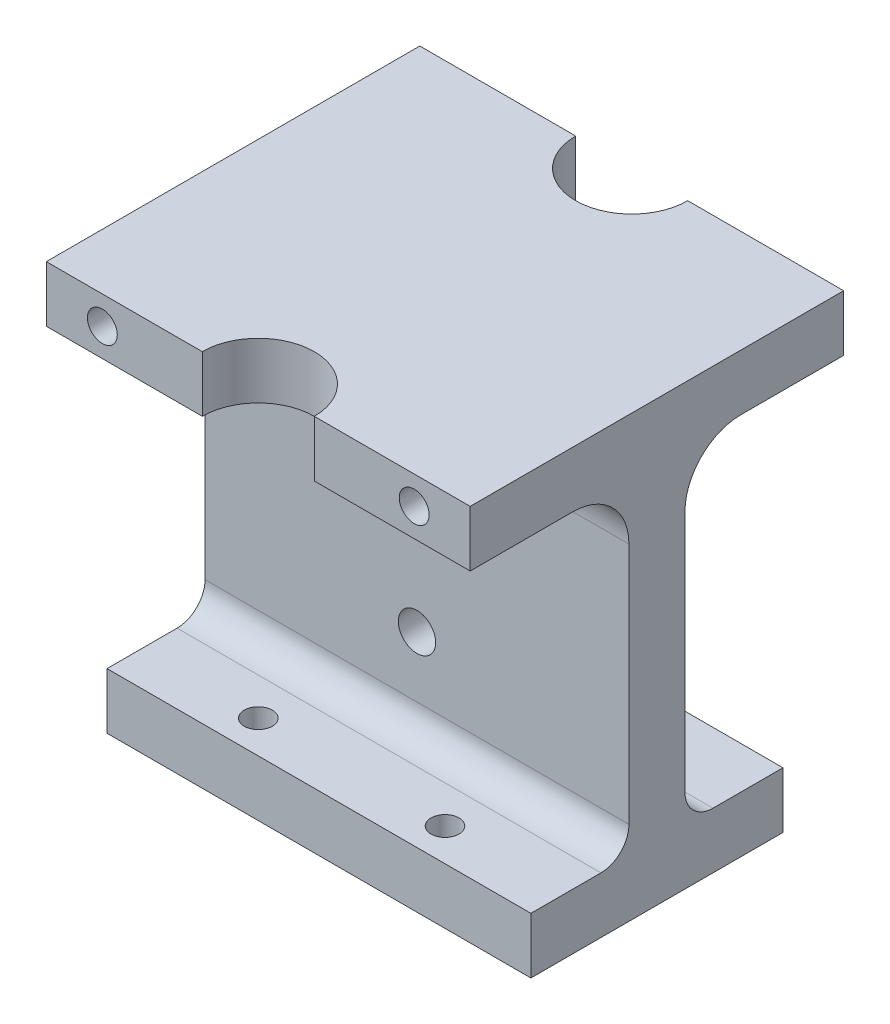
SolidWorks part; units mm, degrees
ref_plane "Płaszczyzna przednia" through (0, 0, 0) normal (0, 0, 1) x (1, 0, 0)
ref_plane "Płaszczyzna górna" through (0, 0, 0) normal (0, 1, 0) x (1, 0, 0)
ref_plane "Płaszczyzna prawa" through (0, 0, 0) normal (1, 0, 0) x (0, 0, -1)
sketch "Sketch1" plane through (0, 0, 0) normal (0, 1, 0) x (1, 0, 0)
  line L1 (0, 0) -> (45.4, 0)
  line L2 (0, 0) -> (0, 27)
  line L3 (0, 27) -> (45.4, 27)
  line L4 (45.4, 0) -> (45.4, 27)
  dimension "D1" = 45.4
  dimension "D2" = 27
extrude "Boss-Extrude1" add sketch "Sketch1" along normal blind 6
sketch "Sketch4" plane through (0, 6, 0) normal (0, 1, 0) x (1, 0, 0)
  line L0 (0, 27) -> (0, 0) construction
  line L1 (0, 16.5) -> (45.4, 16.5)
  line L2 (0, 16.5) -> (0, 10.5)
  line L3 (0, 10.5) -> (45.4, 10.5)
  line L4 (45.4, 16.5) -> (45.4, 10.5)
  line L5 (45.4, 0) -> (45.4, 27) construction
  line L6 (0, 0) -> (45.4, 0) construction
  dimension "D1" = 6
  dimension "D2" = 10.5
extrude "Boss-Extrude2" add sketch "Sketch4" along normal blind 35
sketch "Sketch5" plane through (0, 41, 0) normal (0, 1, 0) x (1, 0, 0)
  line L0 (45.4, 13.5) -> (0, 13.5) construction
  line L1 (45.4, 33.5) -> (28.7, 33.5)
  line L2 (45.4, 33.5) -> (45.4, -6.5)
  line L3 (45.4, -6.5) -> (28.7, -6.5)
  line L4 (0, 33.5) -> (0, -6.5)
  line L5 (45.4, 33.5) -> (0, -6.5) construction
  line L6 (45.4, -6.5) -> (0, 33.5) construction
  line L7 (45.4, 10.5) -> (45.4, 16.5) construction
  line L8 (0, 16.5) -> (0, 10.5) construction
  line L9 (16.7, 33.5) -> (0, 33.5)
  line L10 (16.7, -6.5) -> (0, -6.5)
  line L11 (22.7, 33.5) -> (22.7, -6.5) construction
  line L12 (45.4, 33.5) -> (0, 33.5) construction
  line L13 (15.0168, -6.5) -> (31.9525, -6.5) construction
  arc A0 (16.7, 33.5) -> (28.7, 33.5) centre (22.7, 33.5) ccw
  arc A1 (28.7, -6.5) -> (16.7, -6.5) centre (22.7, -6.5) ccw
  point P4 (22.7, 13.5)
  dimension "D2" = 6
  dimension "D3" = 6
  dimension "D4" = 22.7
  dimension "D1" = 40
extrude "Boss-Extrude3" add sketch "Sketch5" along normal blind 6
fillet "Fillet4" radius 6 2 edges at (22.7, 41, -10.5) (22.7, 41, -16.5)
hole_wizard "Ø3.2 (3.2) Diameter Hole1" positions "Sketch6" profile "Sketch7" hole size "Ø3.2" standard "ANSI Metric" end condition through all
sketch "Sketch6" plane through (0, 0, 6.5) normal (0, 0, 1) x (1, 0, 0)
  line L0 (0, 47) -> (0, 41) construction
  line L1 (0, 41) -> (16.7, 41) construction
  line L2 (45.4, 47) -> (45.4, 41) construction
  point P0 (6, 44)
  point P2 (39.4, 44)
  dimension "D1" = 6
  dimension "D2" = 3
  dimension "D3" = 6
sketch "Sketch7" plane through (6, 44, 6.5) normal (1, 0, 0) x (0, -1, 0)
  line L0 (0, 0) -> (0, 40)
  line L1 (0, 40) -> (1.6, 40)
  line L2 (1.6, 40) -> (1.6, 0)
  line L5 (1.6, 0) -> (0, 0)
  line L11 (0, -6.35) -> (0, 107.95) construction
  dimension "Thru Hole Dia." = 3.2
  dimension "Thru Hole Depth" = 40
ref_plane "Plane4" through (22.7, 0, 0) normal (-1, 0, 0) x (0, 0, 1)
hole_wizard "Ø3.0mm Dowel Hole1" positions "Sketch13" profile "Sketch14" hole size "Ø3.0" standard "ANSI Metric" end condition through all
sketch "Sketch13" plane through (0, 6, 0) normal (0, 1, 0) x (1, 0, 0)
  line L0 (45.4, 27) -> (0, 27) construction
  line L1 (0, 27) -> (0, 16.5) construction
  point P0 (12.7, 23.5)
  point P10 (32.7, 23.5)
  point P11 (32.7, 3.5)
  point P12 (12.7, 3.5)
  dimension "D1" = 3.5
  dimension "D2" = 12.7
  dimension "D3" = 2
  dimension "D4" = 2
sketch "Sketch14" plane through (12.7, 6, -23.5) normal (1, 0, 0) x (0, 0, 1)
  line L0 (0, 0) -> (0, 6)
  line L1 (0, 6) -> (1.5, 6)
  line L2 (1.5, 6) -> (1.5, 0)
  line L5 (1.5, 0) -> (0, 0)
  line L11 (0, -6.35) -> (0, 107.95) construction
  dimension "Thru Hole Dia." = 3
  dimension "Thru Hole Depth" = 6
hole_wizard "Ø4.0mm Dowel Hole1" positions "Sketch15" profile "Sketch16" hole size "Ø4.0" standard "ANSI Metric" end condition through all
sketch "Sketch15" plane through (0, 0, -10.5) normal (0, 0, 1) x (1, 0, 0)
  point P0 (22.7, 15.5)
sketch "Sketch16" plane through (22.7, 15.5, -10.5) normal (1, 0, 0) x (0, -1, 0)
  line L0 (0, 0) -> (0, 23)
  line L1 (0, 23) -> (2, 23)
  line L2 (2, 23) -> (2, 0)
  line L5 (2, 0) -> (0, 0)
  line L11 (0, -6.35) -> (0, 107.95) construction
  dimension "Thru Hole Dia." = 4
  dimension "Thru Hole Depth" = 23
fillet "Fillet5" radius 3 2 edges at (22.7, 6, -10.5) (22.7, 6, -16.5)
